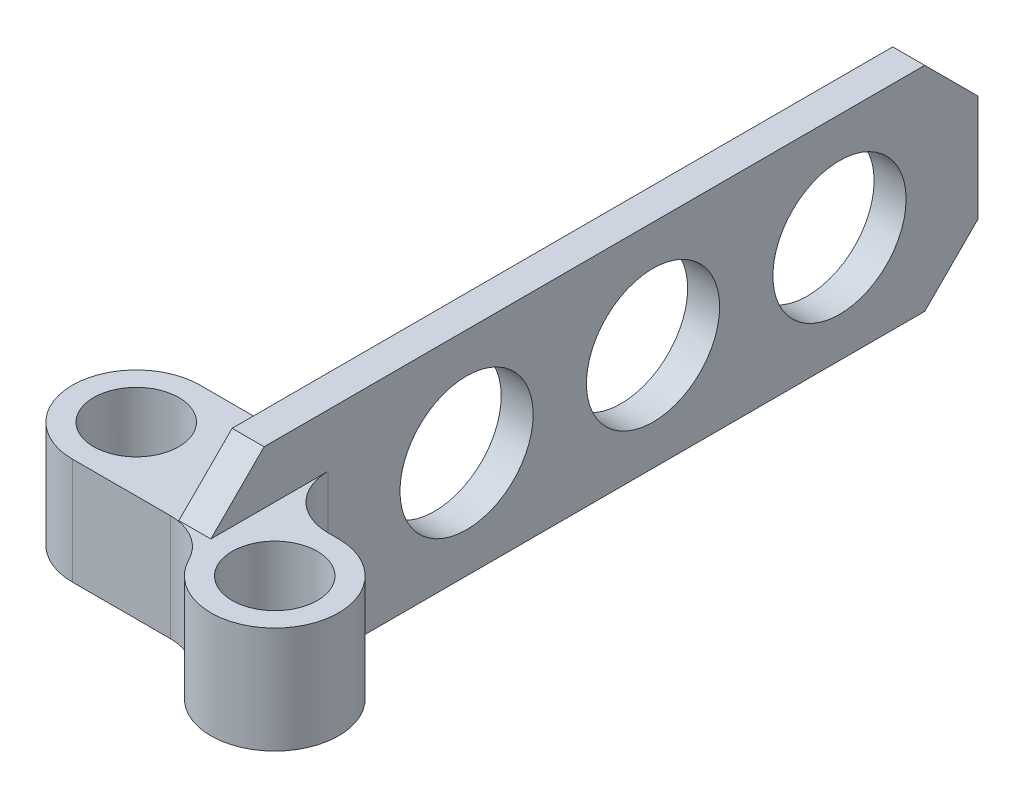
SolidWorks part; units mm, degrees
material "3003 Alloy"
ref_plane "Front Plane" through (0, 0, 0) normal (0, 0, 1) x (1, 0, 0)
ref_plane "Top Plane" through (0, 0, 0) normal (0, 1, 0) x (1, 0, 0)
ref_plane "Right Plane" through (0, 0, 0) normal (1, 0, 0) x (0, 0, -1)
sketch "Sketch1" plane through (0, 0, 0) normal (0, 1, 0) x (1, 0, 0)
  line L0 (-26, 12) -> (-26, 24) construction
  line L1 (-26, 12) -> (-38, 12) construction
  line L2 (0, 0) -> (0, 144)
  line L3 (0, 144) -> (-6, 144)
  line L4 (-6, 24) -> (-6, 144)
  line L5 (-6, 24) -> (-26, 24)
  line L7 (0, 0) -> (-26, 0)
  arc A0 (-26, 24) -> (-26, 0) centre (-26, 12) ccw
  circle A1 centre (-26, 12) radius 8
  dimension "D5" = 16
  dimension "D1" = 6
  dimension "D2" = 120
  dimension "D3" = 24
  dimension "D4" = 20
extrude "Boss-Extrude1" add sketch "Sketch1" along normal blind 40
chamfer "Chamfer1" distance 10 angle 45 2 edges at (-3, 0, -144) (-3, 40, -144)
sketch "Sketch2" plane through (0, 40, 0) normal (0, 1, 0) x (1, 0, 0)
  line L0 (-26, 12) -> (12, 12) construction
  line L1 (12, 12) -> (12, 0) construction
  line L2 (24, 0) -> (24, 24)
  line L9 (0, 24) -> (24, 24)
  line L11 (0, 0) -> (0, 134) construction
  line L12 (-6, 24) -> (-26, 24) construction
  circle A0 centre (12, 0) radius 8
  circle A1 centre (-26, 12) radius 8 construction
  arc A2 (0, 0) -> (24, 0) centre (12, 0) ccw
  arc A3 (-26, 24) -> (-26, 0) centre (-26, 12) ccw construction
extrude "Boss-Extrude2" add sketch "Sketch2" against normal through all
sketch "Sketch4" plane through (0, 0, -24) normal (0, 0, -1) x (-1, 0, 0)
  line L0 (6, 20) -> (46, 20) construction
  line L1 (6, 40) -> (46, 40)
  line L2 (6, 40) -> (6, 30)
  line L3 (6, 30) -> (46, 30)
  line L4 (46, 40) -> (46, 30)
  line L5 (6, 40) -> (6, 0) construction
  line L6 (46, 20) -> (46, 30) construction
  line L7 (46, 0) -> (46, 10)
  line L8 (6, 10) -> (46, 10)
  line L9 (6, 0) -> (6, 10)
  line L10 (6, 0) -> (46, 0)
  line L11 (-40, 0) -> (-40, 10)
  line L12 (0, 40) -> (-40, 40)
  line L13 (0, 40) -> (0, 30)
  line L14 (0, 30) -> (-40, 30)
  line L15 (-40, 40) -> (-40, 30)
  line L16 (0, 10) -> (-40, 10)
  line L17 (0, 0) -> (0, 10)
  line L18 (0, 0) -> (-40, 0)
  dimension "D1" = 20
  dimension "D2" = 40
extrude "Cut-Extrude2" cut sketch "Sketch4" against normal up to next
fillet "Fillet4" radius 10 1 edges at (-6, 20, -24)
sketch "Sketch13" plane through (-6, 0, 0) normal (-1, 0, 0) x (0, 0, 1)
  line L0 (0, 30) -> (-10, 40)
  line L1 (-134, 40) -> (0, 40) construction
  line L2 (-10, 40) -> (0, 40)
  line L3 (0, 40) -> (0, 30)
  line L4 (0, 10) -> (0, 0)
  line L5 (0, 0) -> (-10, 0)
  line L6 (-134, 0) -> (0, 0) construction
  line L7 (-10, 0) -> (0, 10)
extrude "Cut-Extrude9" cut sketch "Sketch13" against normal up to next
sketch "Sketch14" plane through (0, 30, 0) normal (0, 1, 0) x (1, 0, 0)
  line L0 (12, 12) -> (0, 12)
  line L2 (0, 0) -> (0, 24) construction
  line L3 (24, 24) -> (0, 24)
  line L4 (0, 24) -> (0, 12)
  line L5 (24, 24) -> (24, 0)
  arc A0 (24, 0) -> (12, 12) centre (12, 0) ccw
  arc A1 (0, 0) -> (24, 0) centre (12, 0) ccw construction
extrude "Cut-Extrude10" cut sketch "Sketch14" against normal up to next
fillet "Fillet5" radius 10 2 edges at (0, 20, -12) (0, 20, 0)
sketch "Sketch15" plane through (0, 0, 0) normal (1, 0, 0) x (0, 0, -1)
  line L0 (144, 20) -> (22, 20) construction
  line L1 (144, 30) -> (144, 10) construction
  line L2 (22, 30) -> (22, 10) construction
  line L3 (83, 20) -> (83, 40) construction
  line L4 (10, 40) -> (134, 40) construction
  circle A0 centre (83, 20) radius 12.5
  circle A1 centre (118, 20) radius 12.5
  circle A2 centre (48, 20) radius 12.5
  dimension "D1" = 25
  dimension "D2" = 35
extrude "Cut-Extrude11" cut sketch "Sketch15" against normal up to next
